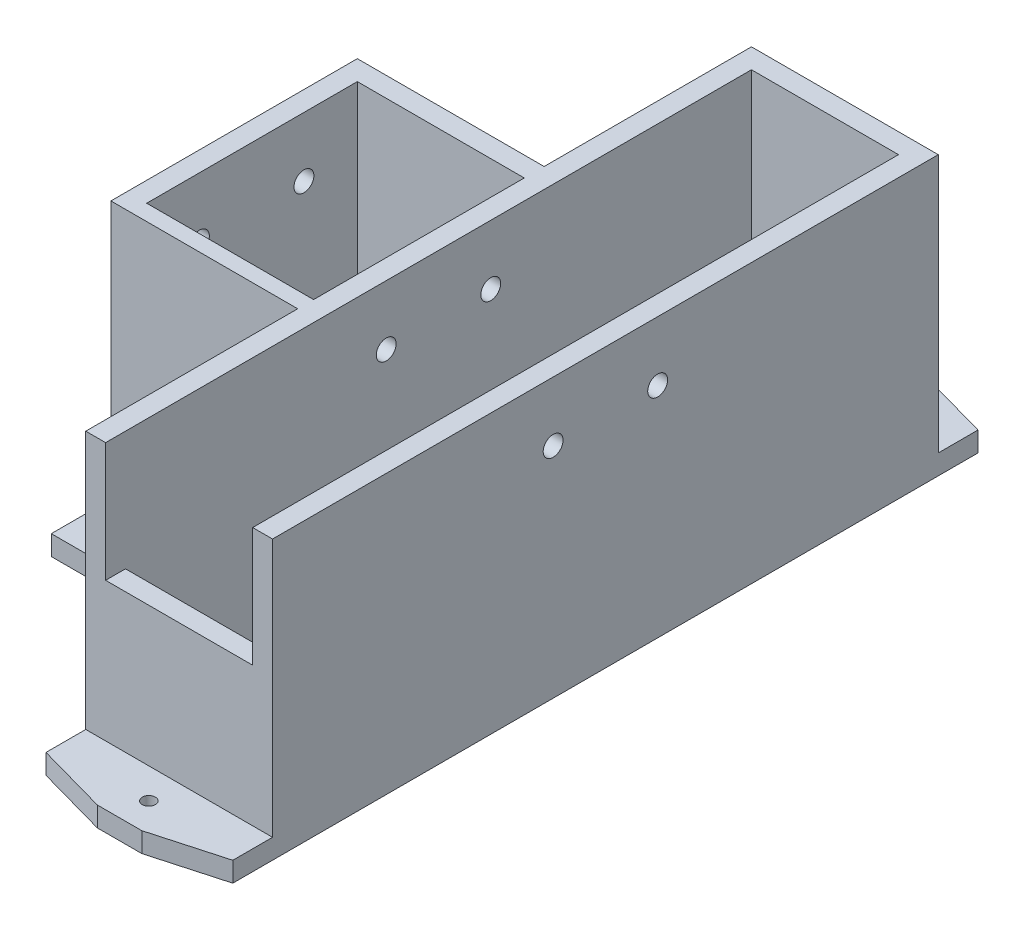
SolidWorks part; units mm, degrees
ref_plane "Plano frontal" through (0, 0, 0) normal (0, 0, 1) x (1, 0, 0)
ref_plane "Plano superior" through (0, 0, 0) normal (0, 1, 0) x (1, 0, 0)
ref_plane "Plano direito" through (0, 0, 0) normal (1, 0, 0) x (0, 0, -1)
sketch "Esboço1" plane through (0, 0, 0) normal (0, 1, 0) x (1, 0, 0)
  line L0 (9.0777, 0.5851) -> (55.4959, 0.5851) construction
  line L1 (0, 0) -> (0, -30.0205) construction
  line L3 (-23.5, 83.75) -> (23.5, 83.75)
  line L4 (-23.5, 83.75) -> (-23.5, -83.75)
  line L5 (-23.5, -83.75) -> (23.5, -83.75)
  line L6 (23.5, 83.75) -> (23.5, -83.75)
  line L7 (-23.5, 83.75) -> (23.5, -83.75) construction
  line L8 (-23.5, -83.75) -> (23.5, 83.75) construction
  line L9 (-70.5, 31.5851) -> (-23.5, 31.5851)
  line L10 (-70.5, 31.5851) -> (-70.5, -30.4149)
  line L11 (-70.5, -30.4149) -> (-23.5, -30.4149)
  line L12 (-23.5, 31.5851) -> (-23.5, -30.4149)
  line L13 (-70.5, 31.5851) -> (-23.5, -30.4149) construction
  line L14 (-70.5, -30.4149) -> (-23.5, 31.5851) construction
  point P1 (0, 0)
  point P11 (-47, 0.5851)
  dimension "D1" = 47
  dimension "D2" = 167.5
  dimension "D3" = 47
  dimension "D4" = 62
extrude "Ressalto-extrusão1" add sketch "Esboço1" along normal blind 70 contours L10 L11 L4 L9 | L6 L3 L4 L5 region at (0, 0, 0) region at (-47, 0, -0.5851)
sketch "Esboço3" plane through (0, 70, 0) normal (0, 1, 0) x (1, 0, 0)
  line L0 (-23.5, 83.75) -> (23.5, 83.75) construction
  line L1 (18.5, -78.75) -> (-18.5, -78.75)
  line L2 (18.5, -78.75) -> (18.5, 78.75)
  line L3 (18.5, 78.75) -> (-18.5, 78.75)
  line L4 (-18.5, -78.75) -> (-18.5, 78.75)
  line L5 (18.5, -78.75) -> (-18.5, 78.75) construction
  line L6 (18.5, 78.75) -> (-18.5, -78.75) construction
  line L7 (-23.5, 83.75) -> (-23.5, 31.5851) construction
  point P0 (0, 0)
  dimension "D1" = 157.5
  dimension "D2" = 5
  dimension "D3" = 37
  dimension "D4" = 5
extrude "Corte-extrusão2" cut sketch "Esboço3" against normal blind 65
sketch "Esboço5" plane through (0, 70, 0) normal (0, 1, 0) x (1, 0, 0)
  line L0 (-18.5, -78.75) -> (18.5, -78.75) construction
  line L1 (-18.5, -62.7828) -> (18.5, -62.7828)
  line L2 (-18.5, -62.7828) -> (-18.5, -94.7172)
  line L3 (-18.5, -94.7172) -> (18.5, -94.7172)
  line L4 (18.5, -62.7828) -> (18.5, -94.7172)
  line L5 (-18.5, -62.7828) -> (18.5, -94.7172) construction
  line L6 (-18.5, -94.7172) -> (18.5, -62.7828) construction
  point P0 (0, -78.75)
  dimension "D1" = 37
extrude "Corte-extrusão3" cut sketch "Esboço5" against normal blind 30
sketch "Esboço11" plane through (0, 0, 0) normal (0, -1, 0) x (1, 0, 0)
  line L0 (-23.5, -83.75) -> (-23.5, -31.5851) construction
  line L1 (-23.5, -83.75) -> (23.5, -83.75)
  line L2 (-23.5, -83.75) -> (-23.5, -98.75)
  line L3 (-23.5, -98.75) -> (23.5, -98.75)
  line L4 (23.5, -83.75) -> (23.5, -98.75)
  line L5 (-23.5, 83.75) -> (23.5, 83.75)
  line L6 (-23.5, 83.75) -> (-23.5, 98.75)
  line L7 (-23.5, 98.75) -> (23.5, 98.75)
  line L8 (23.5, 83.75) -> (23.5, 98.75)
  line L9 (-70.5, -31.5851) -> (-23.5, -31.5851)
  line L10 (-70.5, -31.5851) -> (-70.5, -46.5851)
  line L11 (-70.5, -46.5851) -> (-23.5, -46.5851)
  line L12 (-23.5, -31.5851) -> (-23.5, -46.5851)
  line L13 (-23.5, 30.4149) -> (-23.5, 83.75) construction
  line L14 (-70.5, 30.4149) -> (-23.5, 30.4149)
  line L15 (-70.5, 30.4149) -> (-70.5, 45.4149)
  line L16 (-70.5, 45.4149) -> (-23.5, 45.4149)
  line L17 (-23.5, 30.4149) -> (-23.5, 45.4149)
  dimension "D1" = 15
  dimension "D2" = 15
  dimension "D3" = 15
  dimension "D4" = 15
extrude "Ressalto-extrusão2" add sketch "Esboço11" against normal blind 5
sketch "Esboço12" plane through (0, 5, 0) normal (0, 1, 0) x (1, 0, 0)
  line L0 (-70.5, 46.5851) -> (-23.5, 46.5851) construction
  line L1 (-23.5, -45.4149) -> (-70.5, -45.4149) construction
  line L2 (-70.5, 31.5851) -> (-70.5, 46.5851) construction
  line L4 (-70.5, -45.4149) -> (-70.5, -30.4149) construction
  line L5 (23.5, -98.75) -> (-23.5, -98.75) construction
  line L6 (-23.5, 98.75) -> (23.5, 98.75) construction
  circle A0 centre (-47, -38.0499) radius 1.65
  circle A2 centre (-47, 39.2151) radius 1.65
  circle A4 centre (0, -91.38) radius 1.65
  circle A5 centre (0, 91.38) radius 1.65
  point P20 (0, -98.75)
  dimension "D1" = 3.3
  dimension "D5" = 3.3
  dimension "D11" = 3.3
  dimension "D13" = 3.3
  dimension "D4" = 7.37
  dimension "D8" = 7.365
  dimension "D9" = 23.5
  dimension "D10" = 23.5
  dimension "D12" = 7.37
  dimension "D14" = 7.37
extrude "Corte-extrusão6" cut sketch "Esboço12" against normal through all
sketch "Esboço14" plane through (23.5, 0, 0) normal (1, 0, 0) x (0, 0, -1)
  line L0 (0, 0) -> (0, 98.479) construction
  line L1 (83.75, 70) -> (-83.75, 70) construction
  circle A0 centre (-13.15, 55) radius 2.5
  circle A1 centre (13.15, 55) radius 2.5
  point P7 (0, 0)
  dimension "D1" = 26.3
  dimension "D2" = 5
  dimension "D3" = 5
  dimension "D4" = 13.15
  dimension "D5" = 15
  dimension "D6" = 15
extrude "Corte-extrusão8" cut sketch "Esboço14" against normal through all
sketch "Esboço15" plane through (0, 70, 0) normal (0, 1, 0) x (1, 0, 0)
  line L1 (-65.5, 26.5851) -> (-23.5, 26.5851)
  line L2 (-65.5, 26.5851) -> (-65.5, -26.4149)
  line L3 (-65.5, -26.4149) -> (-23.5, -26.4149)
  line L4 (-23.5, 26.5851) -> (-23.5, -26.4149)
  line L5 (-65.5, 26.5851) -> (-23.5, -26.4149) construction
  line L6 (-65.5, -26.4149) -> (-23.5, 26.5851) construction
  line L7 (-70.5, 31.5851) -> (-23.5, 31.5851) construction
  line L8 (-18.5, 78.75) -> (-18.5, -83.75) construction
  point P0 (-44.5, 0.0851)
  dimension "D1" = 42
  dimension "D2" = 5
  dimension "D3" = 53
  dimension "D4" = 5
extrude "Corte-extrusão10" cut sketch "Esboço15" against normal blind 65
chamfer "Chanfro9" distance 5 angle 74.4 4 edges at (23.5, 2.5, 98.75) (-23.5, 2.5, 98.75) (-23.5, 2.5, -98.75) (23.5, 2.5, -98.75) first distance on face at (23.5, 55, -15.65) first distance on face at (-23.5, 20, 64.5825) first distance on face at (-23.5, 20, -65.1675)
